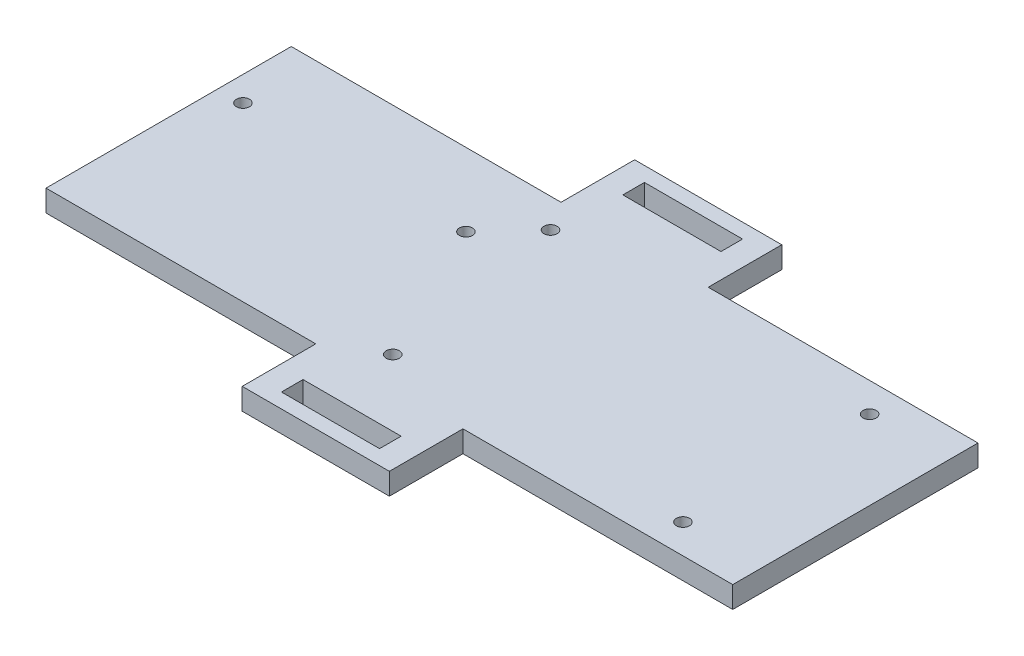
SolidWorks part; units mm, degrees
ref_plane "Front Plane" through (0, 0, 0) normal (0, 0, 1) x (1, 0, 0)
ref_plane "Top Plane" through (0, 0, 0) normal (0, 1, 0) x (1, 0, 0)
ref_plane "Right Plane" through (0, 0, 0) normal (1, 0, 0) x (0, 0, -1)
sketch "Sketch1" plane through (0, 0, 0) normal (0, 1, 0) x (1, 0, 0)
  line L0 (19.05, 31.75) -> (19.05, 50.8)
  line L1 (-88.9, -31.75) -> (-19.05, -31.75)
  line L2 (-88.9, -31.75) -> (-88.9, 31.75)
  line L3 (-88.9, 31.75) -> (-19.05, 31.75)
  line L4 (88.9, -31.75) -> (88.9, 31.75)
  line L5 (-88.9, -31.75) -> (88.9, 31.75) construction
  line L6 (-88.9, 31.75) -> (88.9, -31.75) construction
  line L7 (19.05, 50.8) -> (-19.05, 50.8)
  line L8 (-19.05, 50.8) -> (-19.05, 31.75)
  line L9 (19.05, 31.75) -> (88.9, 31.75)
  line L10 (-88.9, 0) -> (88.9, 0) construction
  line L11 (19.05, -31.75) -> (19.05, -50.8)
  line L12 (19.05, -50.8) -> (-19.05, -50.8)
  line L13 (-19.05, -50.8) -> (-19.05, -31.75)
  line L14 (19.05, -31.75) -> (88.9, -31.75)
  point P0 (0, 0)
  dimension "D1" = 177.8
  dimension "D2" = 63.5
  dimension "D3" = 19.05
  dimension "D4" = 38.1
extrude "Boss-Extrude1" add sketch "Sketch1" along normal blind 5.588
sketch "Sketch2" plane through (0, 5.588, 0) normal (0, 1, 0) x (1, 0, 0)
  line L0 (0, 0) -> (88.9, 0) construction
  line L1 (-12.7, 41.402) -> (12.7, 41.402)
  line L2 (-12.7, 41.402) -> (-12.7, 46.99)
  line L3 (-12.7, 46.99) -> (12.7, 46.99)
  line L4 (12.7, 41.402) -> (12.7, 46.99)
  line L5 (-12.7, 41.402) -> (12.7, 46.99) construction
  line L6 (-12.7, 46.99) -> (12.7, 41.402) construction
  line L7 (88.9, -31.75) -> (88.9, 31.75) construction
  line L8 (-12.7, -46.99) -> (12.7, -41.402) construction
  line L9 (-12.7, -41.402) -> (12.7, -46.99) construction
  line L10 (12.7, -41.402) -> (12.7, -46.99)
  line L11 (-12.7, -46.99) -> (12.7, -46.99)
  line L12 (-12.7, -41.402) -> (-12.7, -46.99)
  line L13 (-12.7, -41.402) -> (12.7, -41.402)
  point P0 (0, 44.196)
  point P5 (0, 0)
  point P15 (0, -44.196)
  dimension "D1" = 5.588
  dimension "D2" = 25.4
  dimension "D3" = 41.402
extrude "Cut-Extrude1" cut sketch "Sketch2" against normal through all
sketch "Sketch3" plane through (0, 5.588, 0) normal (0, 1, 0) x (1, 0, 0)
  point P0 (-14.1986, 24.1681)
  point P1 (68.4276, 24.1681)
  point P3 (68.4276, -24.1681)
  point P5 (-6.7056, -24.1681)
hole_wizard "M3 Clearance Hole1" positions "Sketch4" profile "Sketch5" hole size "M3" standard "ANSI Metric" end condition through all
sketch "Sketch4" plane through (0, 5.588, 0) normal (0, 1, 0) x (1, 0, 0)
  point P0 (-14.1986, 24.1681)
  point P3 (68.4276, 24.1681)
  point P6 (68.4276, -24.1681)
  point P9 (-6.7056, -24.1681)
sketch "Sketch5" plane through (-14.1986, 5.588, -24.1681) normal (1, 0, 0) x (0, 0, 1)
  line L0 (0, 0) -> (0, 5.588)
  line L1 (0, 5.588) -> (1.7, 5.588)
  line L2 (1.7, 5.588) -> (1.7, 0)
  line L5 (1.7, 0) -> (0, 0)
  line L11 (0, -6.35) -> (0, 107.95) construction
  dimension "Thru Hole Dia." = 3.4
  dimension "Thru Hole Depth" = 5.588
hole_wizard "M3 Clearance Hole2" positions "Sketch6" profile "Sketch7" hole size "M3" standard "ANSI Metric" end condition through all
sketch "Sketch6" plane through (0, 5.588, 0) normal (0, 1, 0) x (1, 0, 0)
  point P0 (-24.765, 12.827)
  point P3 (-82.4865, 12.827)
sketch "Sketch7" plane through (-24.765, 5.588, -12.827) normal (1, 0, 0) x (0, 0, 1)
  line L0 (0, 0) -> (0, 5.588)
  line L1 (0, 5.588) -> (1.7, 5.588)
  line L2 (1.7, 5.588) -> (1.7, 0)
  line L5 (1.7, 0) -> (0, 0)
  line L11 (0, -6.35) -> (0, 107.95) construction
  dimension "Thru Hole Dia." = 3.4
  dimension "Thru Hole Depth" = 5.588
